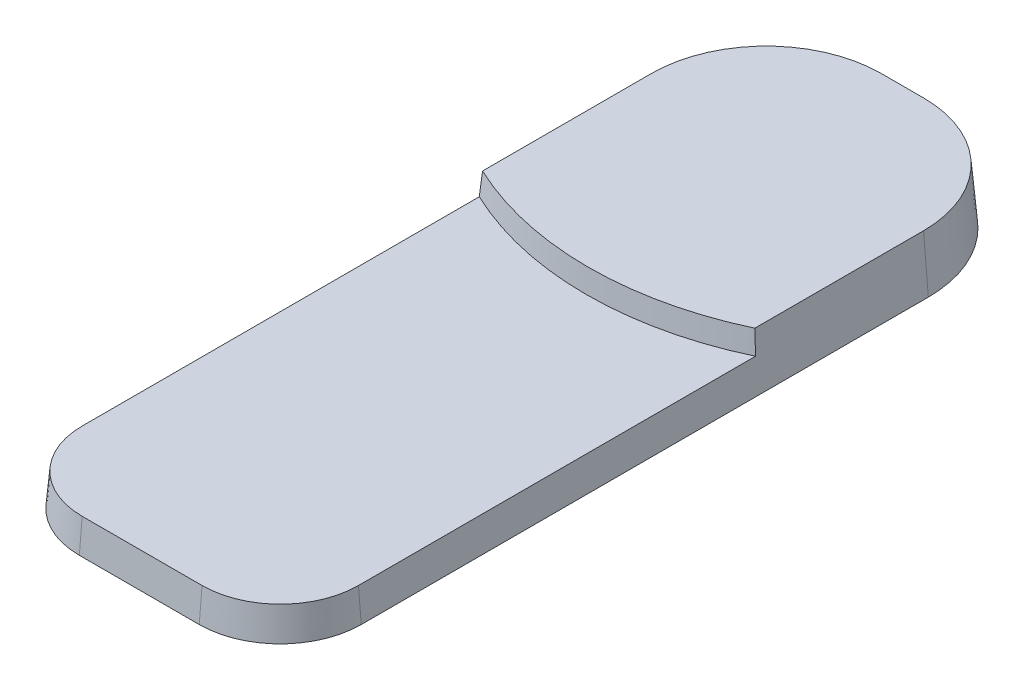
SolidWorks part; units mm, degrees
ref_plane "Front Plane" through (0, 0, 0) normal (0, 0, 1) x (1, 0, 0)
ref_plane "Top Plane" through (0, 0, 0) normal (0, 1, 0) x (1, 0, 0)
ref_plane "Right Plane" through (0, 0, 0) normal (1, 0, 0) x (0, 0, -1)
sketch "Sketch1" plane through (0, 0, 0) normal (0, 1, 0) x (1, 0, 0)
  line L1 (-3.25, 59.25) -> (3.25, 59.25)
  line L2 (-21.75, 40.75) -> (-21.75, -46.75)
  line L3 (-9.25, -59.25) -> (9.25, -59.25)
  line L4 (21.75, 40.75) -> (21.75, -46.75)
  line L5 (-21.75, 59.25) -> (21.75, -59.25) construction
  line L6 (-21.75, -59.25) -> (21.75, 59.25) construction
  arc A0 (3.25, 59.25) -> (21.75, 40.75) centre (3.25, 40.75) cw
  arc A1 (-3.25, 59.25) -> (-21.75, 40.75) centre (-3.25, 40.75) ccw
  arc A2 (9.25, -59.25) -> (21.75, -46.75) centre (9.25, -46.75) ccw
  arc A3 (-9.25, -59.25) -> (-21.75, -46.75) centre (-9.25, -46.75) cw
  arc A4 (-21.75, 14.25) -> (21.75, 14.25) centre (0, 59.2715) ccw
  point P0 (0, 0)
  point P21 (0, 0)
  point P22 (0, 0)
  point P23 (0, 0)
  point P24 (-57.0462, 33.2092)
  point P25 (0, 0)
  point P26 (0, 0)
  dimension "D3" = 18.5
  dimension "D4" = 12.5
  dimension "D5" = 50
  dimension "D1" = 43.5
  dimension "D2" = 118.5
  dimension "D6" = 26.5
extrude "Boss-Extrude1" add sketch "Sketch1" along normal blind 5 draft 5 contours A4 L2 A3 L3 A2 L4 | L2 A4 L4 A0 L1 A1 region at (0, 0, -33.5442) region at (0, 0, 23.4355)
extrude "Boss-Extrude2" add sketch "Sketch1<3>" along normal blind 8.5 draft 5 contours L2 A4 L4 A0 L1 A1 region at (0, 0, -33.5442)
sketch "Sketch1<3>" plane through (0, 0, 0) normal (0, 1, 0) x (1, 0, 0) same geometry as "Sketch1"
